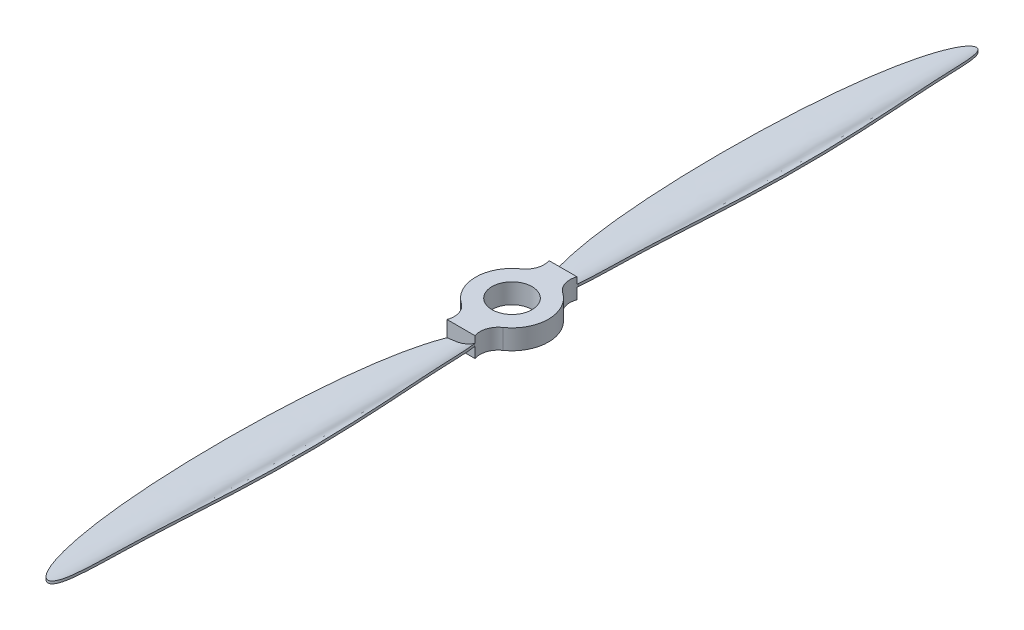
SolidWorks part; units mm, degrees
material "ABS"
ref_plane "Alzado" through (0, 0, 0) normal (0, 0, 1) x (1, 0, 0)
ref_plane "Planta" through (0, 0, 0) normal (0, 1, 0) x (1, 0, 0)
ref_plane "Vista lateral" through (0, 0, 0) normal (1, 0, 0) x (0, 0, -1)
sketch "Croquis1" plane through (0, 0, 0) normal (0, 1, 0) x (1, 0, 0)
  line L0 (0, 10) -> (0, 127) construction
  line L1 (0, -10) -> (0, -127) construction
  line L2 (-10, 0) -> (-127, 0) construction
  arc A0 (-5.705, 8.2129) -> (-5.705, -8.2129) centre (0, 0) ccw
  circle A1 centre (0, 0) radius 5.5
  circle A2 centre (0, 0) radius 127 construction
  arc A3 (-5.705, 8.2129) -> (-3.9833, 14.3385) centre (-8.5576, 12.3194) ccw
  arc A4 (5.705, 8.2129) -> (3.9833, 14.3385) centre (8.5576, 12.3194) cw
  arc A5 (5.705, -8.2129) -> (3.9833, -14.3385) centre (8.5576, -12.3194) ccw
  arc A6 (-5.705, -8.2129) -> (-3.9833, -14.3385) centre (-8.5576, -12.3194) cw
  arc A7 (5.705, -8.2129) -> (5.705, 8.2129) centre (0, 0) ccw
  ellipse E0 centre (0, 68.5) end of major axis (0, 127) minor radius 10.5402 (3.9833, 14.3385) -> (-3.9833, 14.3385) ccw
  ellipse E1 centre (0, -68.5) end of major axis (0, -127) minor radius 10.5402 (3.9833, -14.3385) -> (-3.9833, -14.3385) cw
extrude "Saliente-Extruir1" add sketch "Croquis1" along normal blind 8
ref_plane "Plano1" through (0, 0, 127) normal (0, 0, 1) x (1, 0, 0)
sketch "Croquis2" plane through (0, 0, 127) normal (0, 0, 1) x (1, 0, 0)
  line L0 (-10.5402, 0) -> (-10.5402, 0.7)
  line L1 (-10.5402, 8) -> (-10.5402, 0) construction
  line L2 (10.5402, 7.3) -> (10.5402, 8)
  line L3 (-10.5402, 0.7) -> (-10.5402, 8)
  line L4 (-10.5402, 8) -> (10.5402, 8)
  line L5 (10.5402, 7.3) -> (10.5402, 0)
  line L6 (10.5402, 0) -> (-10.5402, 0)
  line L7 (-12.847, 0) -> (-12.847, 4.5585) construction
  line L8 (-36.2342, 0) -> (-15.1539, 0)
  line L9 (-36.2342, 7.3) -> (-36.2342, 0)
  line L10 (-15.1539, 8) -> (-36.2342, 8)
  line L11 (-15.1539, 0.7) -> (-15.1539, 8)
  line L12 (-36.2342, 7.3) -> (-36.2342, 8)
  line L13 (-15.1539, 0) -> (-15.1539, 0.7)
  spline S0 degree 3 poles (-10.5402, 0.7) (-6.6035, 1.1648) (0.425, 0.4785) (6.2362, 5.6452) (8.9141, 7.8975) (10.5402, 8) knots 0 0 0 0 0.556269 0.795859 1 1 1 1
  spline S1 degree 3 poles (-10.5402, 0) (-6.6035, 0.4648) (0.425, -0.2215) (6.2362, 4.9452) (8.9141, 7.1975) (10.5402, 7.3) knots 0 0 0 0 0.556269 0.795859 1 1 1 1
  spline S2 degree 3 poles (-15.1539, 0) (-19.0905, 0.4648) (-26.119, -0.2215) (-31.9303, 4.9452) (-34.6082, 7.1975) (-36.2342, 7.3) knots 0 0 0 0 0.556269 0.795859 1 1 1 1
  spline S3 degree 3 poles (-15.1539, 0.7) (-19.0905, 1.1648) (-26.119, 0.4785) (-31.9303, 5.6452) (-34.6082, 7.8975) (-36.2342, 8) knots 0 0 0 0 0.556269 0.795859 1 1 1 1
extrude "Cortar-Extruir1" cut sketch "Croquis2" against normal blind 113 contours L3 S0 L4 | S1 L6 L5 region at (5.9137, 2.4194, 127) region at (-2.7074, 4.9134, 127)
ref_plane "Plano2" through (0, 0, -127) normal (0, 0, -1) x (-1, 0, 0)
sketch "Croquis3" plane through (0, 0, -127) normal (0, 0, -1) x (-1, 0, 0)
  line L1 (-10.5402, 0) -> (10.5402, 0)
  line L2 (-10.5402, 7.3) -> (-10.5402, 0)
  line L3 (10.5402, 8) -> (-10.5402, 8)
  line L4 (10.5402, 0.7) -> (10.5402, 8)
  line L5 (-10.5402, 7.3) -> (-10.5402, 8)
  line L6 (10.5402, 0) -> (10.5402, 0.7)
  spline S0 degree 3 poles (10.5402, 0) (6.6035, 0.4648) (-0.425, -0.2215) (-6.2362, 4.9452) (-8.9141, 7.1975) (-10.5402, 7.3) knots 0 0 0 0 0.556269 0.795859 1 1 1 1
  spline S1 degree 3 poles (10.5402, 0.7) (6.6035, 1.1648) (-0.425, 0.4785) (-6.2362, 5.6452) (-8.9141, 7.8975) (-10.5402, 8) knots 0 0 0 0 0.556269 0.795859 1 1 1 1
  point P0 (10.5402, 0)
extrude "Cortar-Extruir2" cut sketch "Croquis3" against normal blind 113 contours L1 S0 L2 | S1 L4 L3 region at (5.9152, 2.4195, -127) region at (-2.7071, 4.9131, -127)
sketch "Sketch1" plane through (0, 8, 0) normal (0, 1, 0) x (1, 0, 0)
  line L1 (11.4411, 16.0582) -> (-11.4411, 16.0582)
  line L2 (11.4411, 16.0582) -> (11.4411, -16.0582)
  line L3 (11.4411, -16.0582) -> (-11.4411, -16.0582)
  line L4 (-11.4411, 16.0582) -> (-11.4411, -16.0582)
  line L5 (11.4411, 16.0582) -> (-11.4411, -16.0582) construction
  line L6 (11.4411, -16.0582) -> (-11.4411, 16.0582) construction
  point P0 (0, 0)
extrude "Cut-Extrude1" cut sketch "Sketch1" against normal blind 2.54
